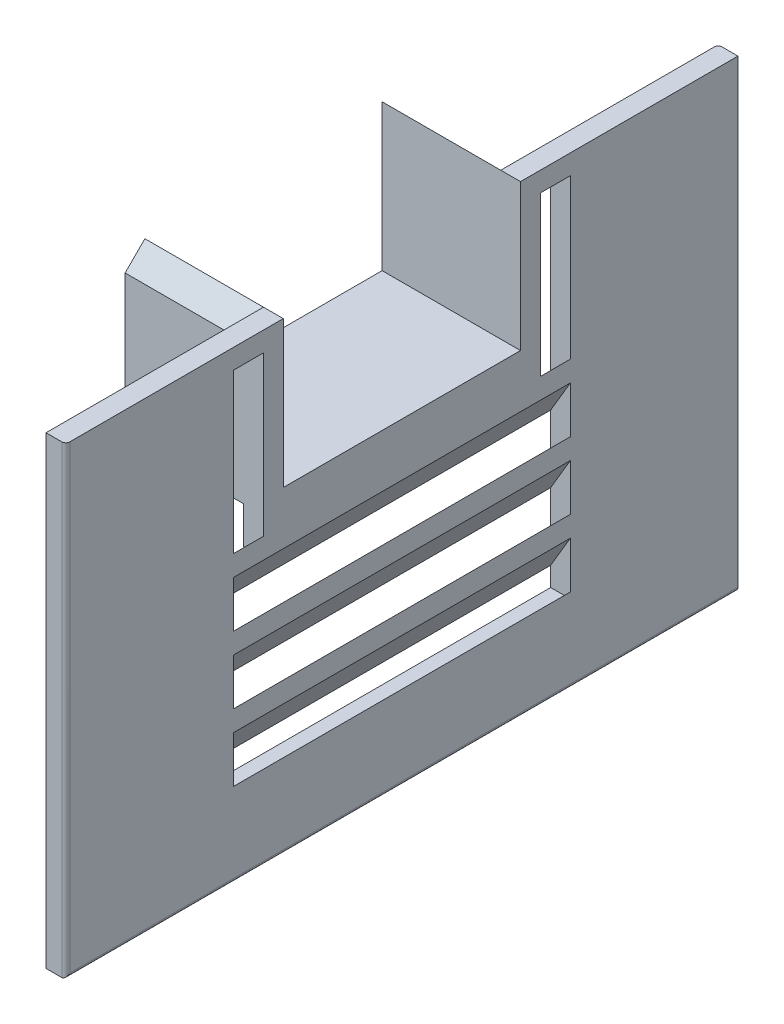
SolidWorks part; units mm, degrees
ref_plane "Front Plane" through (0, 0, 0) normal (0, 0, 1) x (1, 0, 0)
ref_plane "Top Plane" through (0, 0, 0) normal (0, 1, 0) x (1, 0, 0)
ref_plane "Right Plane" through (0, 0, 0) normal (1, 0, 0) x (0, 0, -1)
sketch "Esquisse2" plane through (0, 0, 0) normal (1, 0, 0) x (0, 0, -1)
  line L0 (30, 62.1517) -> (85, 62.1517)
  line L1 (-103.5861, 62.1517) -> (103.5861, 62.1517)
  line L2 (-103.5861, 62.1517) -> (-103.5861, -62.1517)
  line L3 (-103.5861, -62.1517) -> (103.5861, -62.1517)
  line L4 (103.5861, 62.1517) -> (103.5861, -62.1517)
  line L5 (-103.5861, 62.1517) -> (103.5861, -62.1517) construction
  line L6 (-103.5861, -62.1517) -> (103.5861, 62.1517) construction
  line L7 (85, 62.1517) -> (85, -55.2005)
  line L8 (85, -55.2005) -> (0, -55.2005)
  line L9 (0, -55.2005) -> (0, -35.5674)
  line L10 (0, -35.5674) -> (42.6212, -35.5674)
  line L11 (42.6212, -35.5674) -> (42.6212, 57.1517)
  line L12 (42.6212, 57.1517) -> (35, 57.1517)
  line L13 (35, 57.1517) -> (35, 12.1517)
  line L14 (35, 12.1517) -> (0, 12.1517)
  line L15 (0, 25.1517) -> (30, 25.1517)
  line L16 (30, 25.1517) -> (30, 62.1517)
  line L17 (0, 25.1517) -> (0, 12.1517)
  point P0 (0, 0)
  dimension "D1" = 55
  dimension "D2" = 85
  dimension "D3" = 30
  dimension "D5" = 37
  dimension "D6" = 5
  dimension "D7" = 5
extrude "Boss.-Extru.3" add sketch "Esquisse2" along normal blind 5 contours L15 L17 L14 L13 L12 L11 L10 L9 L8 L7 L0 L16 region at (0, -0.2861, -54.042)
mirror "Symétrie1" about plane through (0, 0, 0) normal (0, 0, 1) of "Boss.-Extru.3"
sketch "Esquisse5" plane through (0, 0, -42.6212) normal (0, 0, 1) x (1, 0, 0)
  line L0 (0, -30.7031) -> (5, -22.2492)
  line L1 (0, -35.5674) -> (0, 57.1517) construction
  line L2 (5, -35.5674) -> (5, 57.1517) construction
sketch "Esquisse6" plane through (0, 0, 0) normal (1, 0, 0) x (0, 0, -1)
  line L0 (-42.6212, -35.5674) -> (-42.6212, 57.1517) construction
  line L1 (42.6212, -30.7031) -> (-42.6212, -30.7031)
  line L2 (42.6212, -30.7031) -> (42.6212, -25.4858)
  line L3 (42.6212, -25.4858) -> (-42.6212, -25.4858)
  line L4 (-42.6212, -30.7031) -> (-42.6212, -25.4858)
sweep "Balayage5" add profiles "Esquisse6" path "Esquisse5"
pattern_linear "Répétition linéaire1" count 3 spacing 17 along (0, 1, 0) count 2 spacing 17 along (0, -1, 0) of "Balayage5" pattern seed only yes
fillet "Congé1" radius 1 3 edges at (0, 3.4756, -85) (5, -55.2005, 0) (5, 3.4756, 85)
sketch "Esquisse8" plane through (0, 0, 0) normal (-1, 0, 0) x (0, 0, 1)
  line L0 (-30, 62.1517) -> (-30, 25.1517)
  line L1 (-30, 25.1517) -> (30, 25.1517)
  line L2 (30, 25.1517) -> (-30, 25.1517) construction
  line L3 (30, 25.1517) -> (30, 62.1517) construction
  line L4 (30, 25.1517) -> (30, 62.1517)
  line L5 (30, 62.1517) -> (35, 57.1517)
  line L6 (35, 57.1517) -> (35, 21.5653)
  line L7 (35, 57.1517) -> (35, 12.1517) construction
  line L8 (35, 21.5653) -> (-35, 21.5653)
  line L9 (-35, 57.1517) -> (-35, 12.1517) construction
  line L10 (-35, 21.5653) -> (-35, 57.1517)
  line L11 (-35, 57.1517) -> (-30, 62.1517)
extrude "Boss.-Extru.5" add sketch "Esquisse8" along normal blind 30
